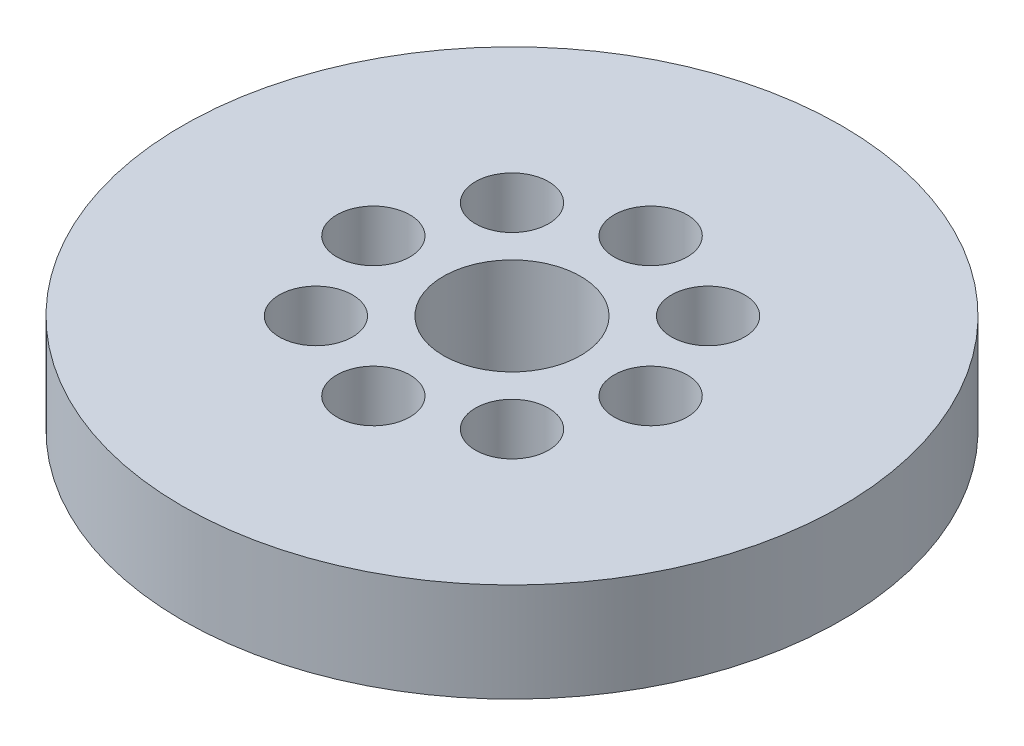
SolidWorks part; units mm, degrees
ref_plane "Front Plane" through (0, 0, 0) normal (0, 0, 1) x (1, 0, 0)
ref_plane "Top Plane" through (0, 0, 0) normal (0, 1, 0) x (1, 0, 0)
ref_plane "Right Plane" through (0, 0, 0) normal (1, 0, 0) x (0, 0, -1)
sketch "Sketch1" plane through (0, 0, 0) normal (0, 1, 0) x (1, 0, 0)
  circle A0 centre (0, 0) radius 60
  dimension "FLANGE_OD" = 120
extrude "Boss-Extrude1" add sketch "Sketch1" along normal blind 18
sketch "Sketch2" plane through (0, 0, 0) normal (0, 1, 0) x (1, 0, 0)
  circle A0 centre (0, 0) radius 12.5
  dimension "BORE_D" = 25
extrude "Cut-Extrude1" cut sketch "Sketch2" along normal through all
sketch "Sketch3" plane through (0, 18, 0) normal (0, 1, 0) x (1, 0, 0)
  circle A0 centre (0, 0) radius 25.2421 construction
  circle A1 centre (-25.2421, 0) radius 6.6541
  dimension "BOLT_D" = 13.3082
  dimension "BOLT_PCD" = 50.4842
extrude "Cut-Extrude2" cut sketch "Sketch3" against normal blind 12.4802
pattern_circular "CirPattern1" count 8 over 360 about axis through (0, 0, 0) along (0, 1, 0) of "Cut-Extrude2"
